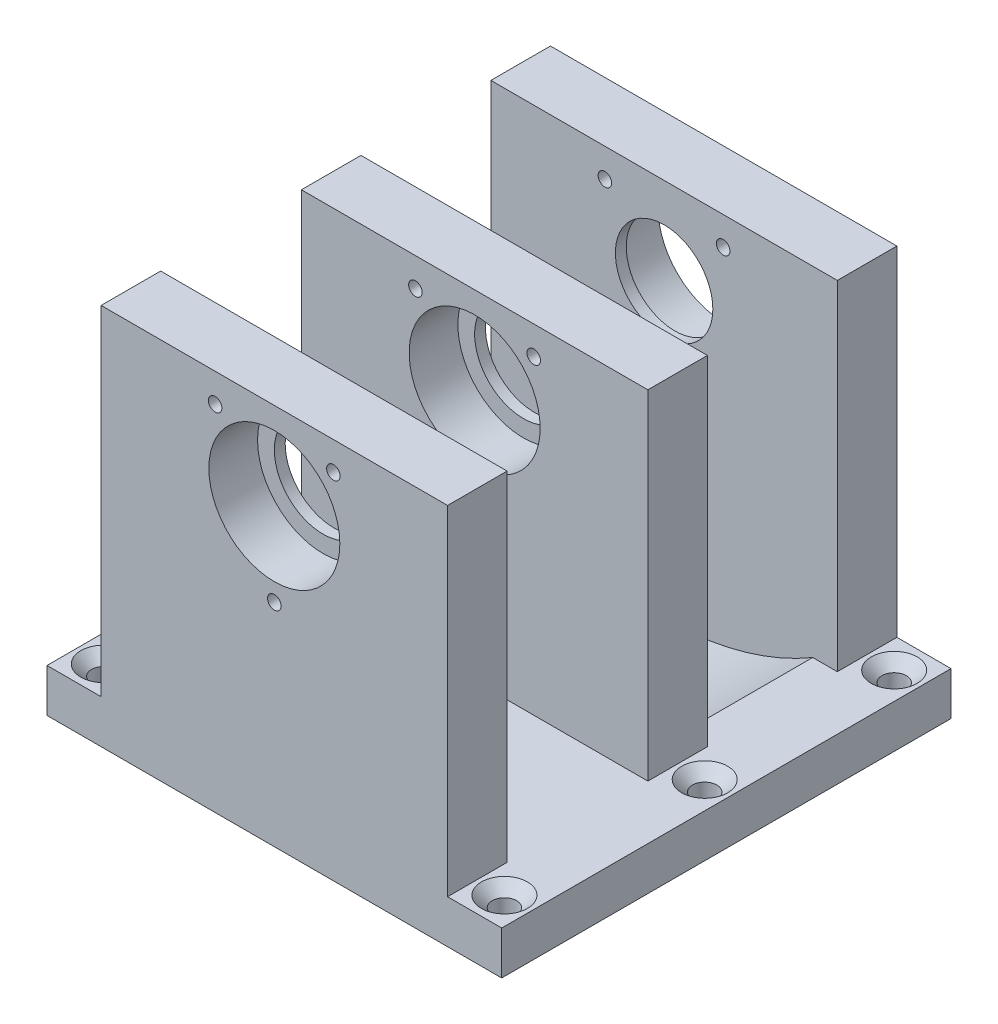
SolidWorks part; units mm, degrees
material "PET"
ref_plane "Piano frontale" through (0, 0, 0) normal (0, 0, 1) x (1, 0, 0)
ref_plane "Piano superiore" through (0, 0, 0) normal (0, 1, 0) x (1, 0, 0)
ref_plane "Piano destro" through (0, 0, 0) normal (1, 0, 0) x (0, 0, -1)
sketch "Schizzo1" plane through (0, 0, 0) normal (0, 0, 1) x (1, 0, 0)
  line L0 (-16.1, 0) -> (0, 0) construction
  line L1 (-6.1713, 16.1) -> (6.1713, 16.1)
  line L3 (-17, -54.5) -> (17, -54.5)
  line L5 (0, 0) -> (16.1, 0) construction
  line L7 (-17, -54.5) -> (-42, -54.5)
  line L11 (17, -54.5) -> (42, -54.5)
  line L16 (42, -54.5) -> (42, -46.5)
  line L18 (-42, -54.5) -> (-42, -46.5)
  line L20 (42, -46.5) -> (32, -46.5)
  line L22 (-42, -46.5) -> (-32, -46.5)
  line L24 (-6.1713, 16.1) -> (-16.1713, 16.1)
  line L26 (6.1713, 16.1) -> (16.1713, 16.1)
  line L28 (-32, -46.5) -> (-32, 16.1)
  line L29 (-32, 16.1) -> (-16.1713, 16.1)
  line L30 (32, -46.5) -> (32, 16.1)
  line L31 (32, 16.1) -> (16.1713, 16.1)
  circle A0 centre (0, 0) radius 12.1
  point P13 (0, -54.5)
  point P14 (0, 16.1)
  dimension "D1" = 24.2
  dimension "D3" = 25
  dimension "D7" = 8
  dimension "D2" = 16.1
  dimension "D5" = 54.5
  dimension "D6" = 34
  dimension "D8" = 10
  dimension "D9" = 10
extrude "Estrusione-Estrusione1" add sketch "Schizzo1" along normal blind 11
sketch "Schizzo2" plane through (0, 0, 11) normal (0, 0, 1) x (1, 0, 0)
  circle A0 centre (0, 0) radius 9
  circle A1 centre (0, 0) radius 12.1
  dimension "D1" = 18
extrude "Estrusione-Estrusione2" add sketch "Schizzo2" against normal blind 2
sketch "Schizzo3" plane through (0, -46.5, 0) normal (0, 1, 0) x (1, 0, 0)
  line L0 (32, -11) -> (42, 0) construction
  line L1 (-42, -11) -> (-32, 0) construction
  circle A0 centre (37, -5.5) radius 2.25
  circle A1 centre (-37, -5.5) radius 2.25
  dimension "D1" = 4.5
extrude "Taglio-Estrusione1" cut sketch "Schizzo3" against normal through all
chamfer "Smusso1" distance 2 angle 45 2 edges at (-37, -46.5, 7.75) (37, -46.5, 7.75)
sketch "Schizzo4" plane through (0, 0, 0) normal (0, 0, -1) x (-1, 0, 0)
  line L0 (-8.5791, 8.5329) -> (-13.2424, 13.1711) construction
  line L1 (8.6056, 8.5061) -> (13.2834, 13.1299) construction
  line L2 (0, -12.1) -> (0, -18.6772) construction
  arc A0 (-6.1713, 16.1) -> (-16.1713, 6.1) centre (-6.1713, 6.1) ccw construction
  arc A1 (16.1, 4.9079) -> (6.1713, 16.1) centre (6.1713, 6.1) ccw construction
  circle A2 centre (0, 0) radius 12.1 construction
  circle A3 centre (0, 0) radius 12.1 construction
  circle A4 centre (-10.9107, 10.852) radius 1.25
  circle A5 centre (10.9445, 10.818) radius 1.25
  circle A6 centre (0, -15.3886) radius 1.25
  dimension "D1" = 2.5
extrude "Taglio-Estrusione2" cut sketch "Schizzo4" against normal through all
sketch "Schizzo5" plane through (0, 0, 11) normal (0, 0, 1) x (1, 0, 0)
  line L1 (-42, -46.5) -> (42, -46.5)
  line L2 (-42, -46.5) -> (-42, -54.5)
  line L3 (-42, -54.5) -> (42, -54.5)
  line L4 (42, -46.5) -> (42, -54.5)
  circle A0 centre (0, 0) radius 54
  line M4 (-42, -54.5) -> (42, -54.5)
  line M5 (42, -54.5) -> (42, -46.5)
  line M6 (42, -46.5) -> (32, -46.5)
  line M12 (-32, -46.5) -> (-42, -46.5)
  line M13 (-42, -46.5) -> (-42, -54.5)
  dimension "D1" = 108
extrude "Estrusione-Estrusione4" add sketch "Schizzo5" along normal blind 24 contours A0 L1 M12 M13 M4 M5 M6 region at (-37, -47.3438, 11)
sketch "Schizzo7" plane through (0, 0, 35) normal (0, 0, 1) x (1, 0, 0)
  line L8 (42, -54.5) -> (42, -46.5)
  line L9 (-42, -54.5) -> (42, -54.5)
  line L10 (-42, -46.5) -> (-42, -54.5)
  line L11 (-32, -46.5) -> (-42, -46.5)
  line L13 (32, 16.1) -> (-32, 16.1)
  line L15 (42, -46.5) -> (32, -46.5)
  line L16 (42, -54.5) -> (42, -46.5)
  line L17 (-42, -54.5) -> (42, -54.5)
  line L18 (-42, -46.5) -> (-42, -54.5)
  line L19 (-32, -46.5) -> (-42, -46.5)
  line L21 (32, 16.1) -> (-32, 16.1)
  line L23 (42, -46.5) -> (32, -46.5)
  line L28 (-32, 16.1) -> (-32, -46.5)
  line L29 (-32, 16.1) -> (-32, -46.5)
  line L30 (32, -46.5) -> (32, 16.1)
  line L32 (32, -46.5) -> (32, 16.1)
  circle A0 centre (10.9107, 10.852) radius 1.25 construction
  circle A1 centre (10.9107, 10.852) radius 1.25
  circle A6 centre (0, 0) radius 9 construction
  circle A7 centre (0, -15.3886) radius 1.25 construction
  circle A8 centre (-10.9445, 10.818) radius 1.25 construction
  circle A9 centre (0, 0) radius 9
  circle A10 centre (0, -15.3886) radius 1.25
  circle A11 centre (-10.9445, 10.818) radius 1.25
  dimension "D1" = 0
extrude "Estrusione-Estrusione5" add sketch "Schizzo7" along normal blind 2
sketch "Schizzo8" plane through (0, 0, 37) normal (0, 0, 1) x (1, 0, 0)
  line L8 (42, -46.5) -> (32, -46.5)
  line L9 (32, -46.5) -> (32, 16.1)
  line L10 (32, 16.1) -> (-32, 16.1)
  line L11 (32, -46.5) -> (32, 16.1)
  line L12 (-32, -46.5) -> (-42, -46.5)
  line L13 (-42, -46.5) -> (-42, -54.5)
  line L14 (-42, -54.5) -> (42, -54.5)
  line L15 (42, -54.5) -> (42, -46.5)
  line L16 (42, -46.5) -> (32, -46.5)
  line L18 (32, 16.1) -> (-32, 16.1)
  line L20 (-32, -46.5) -> (-42, -46.5)
  line L21 (-42, -46.5) -> (-42, -54.5)
  line L22 (-42, -54.5) -> (42, -54.5)
  line L23 (42, -54.5) -> (42, -46.5)
  line L24 (-32, 16.1) -> (-32, -46.5)
  line L25 (-32, 16.1) -> (-32, -46.5)
  circle A0 centre (0, 0) radius 12.1 construction
  circle A1 centre (10.9107, 10.852) radius 1.25 construction
  circle A6 centre (0, -15.3886) radius 1.25 construction
  circle A7 centre (-10.9445, 10.818) radius 1.25 construction
  circle A8 centre (0, 0) radius 12.1
  circle A9 centre (10.9107, 10.852) radius 1.25
  circle A10 centre (0, -15.3886) radius 1.25
  circle A11 centre (-10.9445, 10.818) radius 1.25
  dimension "D1" = 0
extrude "Estrusione-Estrusione6" add sketch "Schizzo8" along normal blind 9
sketch "Schizzo10" plane through (0, 0, 46) normal (0, 0, 1) x (1, 0, 0)
  line L1 (-42, -46.5) -> (42, -46.5)
  line L2 (-42, -46.5) -> (-42, -54.5)
  line L3 (-42, -54.5) -> (42, -54.5)
  line L4 (42, -46.5) -> (42, -54.5)
extrude "Estrusione-Estrusione8" add sketch "Schizzo10" along normal blind 26
sketch "Schizzo11" plane through (0, 0, 72) normal (0, 0, 1) x (1, 0, 0)
  line L4 (-32, -46.5) -> (32, -46.5)
  line L5 (32, -46.5) -> (32, 16.1)
  line L6 (32, 16.1) -> (-32, 16.1)
  line L7 (32, -46.5) -> (32, 16.1)
  line L8 (-32, -46.5) -> (32, -46.5)
  line L10 (32, 16.1) -> (-32, 16.1)
  line L12 (-42, -46.5) -> (-42, -54.5)
  line L13 (-42, -54.5) -> (42, -54.5)
  line L14 (42, -54.5) -> (42, -46.5)
  line L15 (42, -46.5) -> (-42, -46.5)
  line L16 (-42, -46.5) -> (-42, -54.5)
  line L17 (-42, -54.5) -> (42, -54.5)
  line L18 (42, -54.5) -> (42, -46.5)
  line L19 (42, -46.5) -> (-42, -46.5)
  line L20 (-32, 16.1) -> (-32, -46.5)
  line L21 (-32, 16.1) -> (-32, -46.5)
  circle A0 centre (0, -15.3886) radius 1.25 construction
  circle A1 centre (10.9107, 10.852) radius 1.25 construction
  circle A6 centre (-10.9445, 10.818) radius 1.25 construction
  circle A7 centre (0, 0) radius 12.1 construction
  circle A8 centre (0, -15.3886) radius 1.25
  circle A9 centre (10.9107, 10.852) radius 1.25
  circle A10 centre (-10.9445, 10.818) radius 1.25
  circle A11 centre (0, 0) radius 12.1
  line M11 (-42, -46.5) -> (-42, -54.5)
  line M12 (-42, -54.5) -> (42, -54.5)
  line M13 (42, -54.5) -> (42, -46.5)
  line M14 (42, -46.5) -> (-42, -46.5)
  dimension "D1" = 0
  dimension "D2" = 0
extrude "Estrusione-Estrusione9" add sketch "Schizzo11" along normal blind 9 contours M14 M11 M12 M13 | L10 A11 A10 A9 A8 M14 region at (0, -17.2517, 72) region at (0, -50.5, 72)
sketch "Schizzo12" plane through (0, 0, 81) normal (0, 0, 1) x (1, 0, 0)
  line L8 (42, -46.5) -> (32, -46.5)
  line L9 (32, -46.5) -> (32, 16.1)
  line L10 (32, 16.1) -> (-32, 16.1)
  line L11 (32, -46.5) -> (32, 16.1)
  line L12 (-32, -46.5) -> (-42, -46.5)
  line L13 (-42, -46.5) -> (-42, -54.5)
  line L14 (-42, -54.5) -> (42, -54.5)
  line L15 (42, -54.5) -> (42, -46.5)
  line L16 (42, -46.5) -> (32, -46.5)
  line L18 (32, 16.1) -> (-32, 16.1)
  line L20 (-32, -46.5) -> (-42, -46.5)
  line L21 (-42, -46.5) -> (-42, -54.5)
  line L22 (-42, -54.5) -> (42, -54.5)
  line L23 (42, -54.5) -> (42, -46.5)
  line L24 (-32, 16.1) -> (-32, -46.5)
  line L25 (-32, 16.1) -> (-32, -46.5)
  circle A0 centre (10.9107, 10.852) radius 1.25 construction
  circle A1 centre (-10.9445, 10.818) radius 1.25
  circle A2 centre (-10.9445, 10.818) radius 1.25
  circle A3 centre (0, -15.3886) radius 1.25
  circle A4 centre (0, -15.3886) radius 1.25
  circle A6 centre (10.9107, 10.852) radius 1.25
  circle A8 centre (0, 0) radius 12.1 construction
  circle A9 centre (0, 0) radius 12.1
  dimension "D1" = 0
  dimension "D2" = 0
  dimension "D3" = 0
extrude "Estrusione-Estrusione10" add sketch "Schizzo12" along normal blind 2
sketch "Schizzo13" plane through (0, -46.5, 0) normal (0, 1, 0) x (1, 0, 0)
  line L0 (32, -46) -> (42, -35)
  line L1 (42, -83) -> (42, 0) construction
  line L2 (32, -72) -> (42, -83)
  line L3 (-32, -35) -> (-42, -46)
  line L4 (-42, -83) -> (-42, 0) construction
  line L5 (-32, -72) -> (-42, -83)
  circle A0 centre (-37, -40.5) radius 2.25
  circle A1 centre (-37, -77.5) radius 2.25
  circle A2 centre (37, -40.5) radius 2.25
  circle A3 centre (37, -77.5) radius 2.25
  circle A4 centre (-37, -5.5) radius 2.25 construction
extrude "Taglio-Estrusione3" cut sketch "Schizzo13" against normal through all contours L0 A2 | L0 A2 | L3 A0 | L3 A0 | L5 A1 | L5 A1 | L2 A3 | L2 A3 region at (36.2934, -46.5, 39.8576) region at (37.7066, -46.5, 41.1424) region at (37.7066, -46.5, 76.8576) region at (36.2934, -46.5, 78.1424) region at (-36.2934, -46.5, 41.1424) region at (-37.7066, -46.5, 39.8576) region at (-36.2934, -46.5, 78.1424) region at (-37.7066, -46.5, 76.8576)
chamfer "Smusso2" distance 2 angle 45 4 edges at (-37, -46.5, 42.75) (-37, -46.5, 79.75) (37, -46.5, 79.75) (37, -46.5, 42.75)
sketch "Schizzo14" plane through (0, 0, 72) normal (0, 0, -1) x (-1, 0, 0)
  circle A0 centre (0, 0) radius 12.1 construction
  circle A1 centre (0, 0) radius 12.1
  circle A2 centre (0, 0) radius 9
  dimension "D1" = 18
extrude "Estrusione-Estrusione11" add sketch "Schizzo14" against normal blind 2
